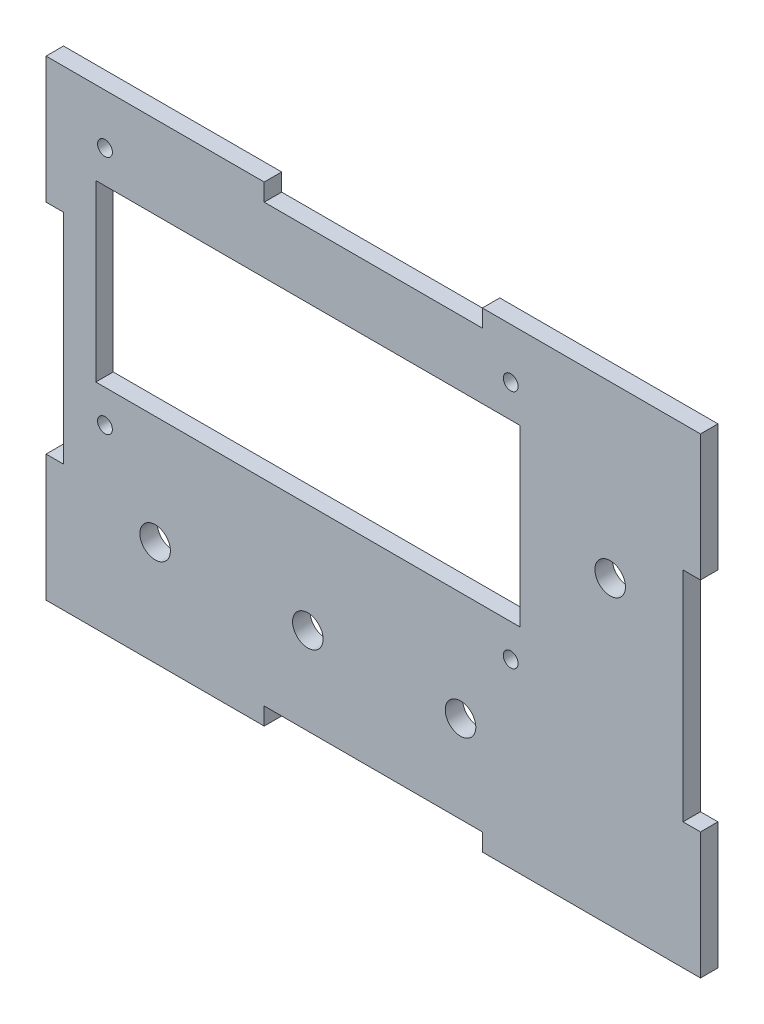
SolidWorks part; units mm, degrees
ref_plane "Front Plane" through (0, 0, 0) normal (0, 0, 1) x (1, 0, 0)
ref_plane "Top Plane" through (0, 0, 0) normal (0, 1, 0) x (1, 0, 0)
ref_plane "Right Plane" through (0, 0, 0) normal (1, 0, 0) x (0, 0, -1)
sketch "Sketch1" plane through (0, 0, 0) normal (0, 0, 1) x (1, 0, 0)
  line L1 (-75, -54) -> (75, -54)
  line L2 (-75, -54) -> (-75, 54)
  line L3 (-75, 54) -> (75, 54)
  line L4 (75, -54) -> (75, 54)
  line L5 (-75, -54) -> (75, 54) construction
  line L6 (-75, 54) -> (75, -54) construction
  point P0 (0, 0)
  dimension "D1" = 150
  dimension "D2" = 108
extrude "Plate" add sketch "Sketch1" along normal blind 4
sketch "Sketch2" plane through (0, 0, 0) normal (0, 0, -1) x (-1, 0, 0)
  line L1 (-33.6, -5) -> (63.6, -5)
  line L2 (-33.6, -5) -> (-33.6, 35)
  line L3 (-33.6, 35) -> (63.6, 35)
  line L4 (63.6, -5) -> (63.6, 35)
  line L5 (-33.6, -5) -> (63.6, 35) construction
  line L6 (-33.6, 35) -> (63.6, -5) construction
  point P0 (15, 15)
  dimension "D1" = 97.2
  dimension "D2" = 40
  dimension "D3" = 15
  dimension "D4" = 15
extrude "Screen slot" cut sketch "Sketch2" against normal through all
sketch "Screen screw hole position" plane through (0, 0, 0) normal (0, 0, -1) x (-1, 0, 0)
  line L0 (63.6, -5) -> (63.6, 35) construction
  line L1 (-33.6, -5) -> (63.6, -5) construction
  line L2 (-33.6, 35) -> (-33.6, -5) construction
  line L3 (63.6, 35) -> (-33.6, 35) construction
  line L4 (63.6, -5) -> (63.6, 35)
  line L5 (-33.6, -5) -> (63.6, -5)
  line L6 (-33.6, 35) -> (-33.6, -5)
  line L7 (63.6, 35) -> (-33.6, 35)
  line L8 (-33.6, 35) -> (63.6, -5) construction
  line L10 (-31.5, -12.5) -> (61.5, -12.5)
  line L11 (-31.5, -12.5) -> (-31.5, 42.5)
  line L12 (-31.5, 42.5) -> (61.5, 42.5)
  line L13 (61.5, -12.5) -> (61.5, 42.5)
  line L14 (-31.5, -12.5) -> (61.5, 42.5) construction
  line L15 (-31.5, 42.5) -> (61.5, -12.5) construction
  point P3 (15, 15)
  dimension "D1" = 93
  dimension "D2" = 55
hole_wizard "Screen screw holes" positions "3DSketch1" profile "Sketch5" countersink size "M3" standard "ISO" end condition up to next
sketch3d "3DSketch1"
  point P0 (31.5, 42.5, 0)
  point P3 (-61.5, 42.5, 0)
  point P6 (-61.5, -12.5, 0)
  point P9 (31.5, -12.5, 0)
sketch "Sketch5" plane through (31.5, 42.5, 0) normal (1, 0, 0) x (0, 1, 0)
  line L0 (0, 0) -> (0, 4)
  line L1 (0, 4) -> (1.7, 4)
  line L2 (1.7, 4) -> (1.7, 1.45)
  line L3 (1.7, 1.45) -> (3.15, 0)
  line L5 (3.15, 0) -> (0, 0)
  line L6 (-1.7, 1.45) -> (-3.15, 0) construction
  line L11 (0, -6.35) -> (0, 107.95) construction
  dimension "Thru Hole Dia." = 3.4
  dimension "Thru Hole Depth" = 4
  dimension "Near C'Sink Dia." = 6.3
  dimension "Near C'Sink Angle" = 90
sketch "Sketch6" plane through (0, 0, 0) normal (0, 0, -1) x (-1, 0, 0)
  line L0 (-75, -54) -> (-75, 54) construction
  line L1 (-33.6, 35) -> (-75, 35)
  line L2 (-33.6, 35) -> (-33.6, -5)
  line L3 (-33.6, -5) -> (-75, -5)
  line L4 (-75, 35) -> (-75, -5)
  line L5 (-75, 35) -> (-33.6, -5) construction
  line L6 (15, -5) -> (15, -30)
  line L7 (-33.6, -5) -> (63.6, -5) construction
  line L8 (15, -30) -> (50, -30)
  line L9 (15, -30) -> (-20, -30)
  point P7 (-54.3, 15)
  point P15 (37.915, -28.8748)
  dimension "D1" = 25
  dimension "D2" = 35
hole_wizard "Knob holes" positions "3DSketch2" profile "Sketch7" hole size "Ø6.0" standard "ISO" end condition up to next
sketch3d "3DSketch2"
  point P0 (20, -30, 0)
  point P3 (-15, -30, 0)
  point P6 (-50, -30, 0)
  point P9 (54.3, 15, 0)
sketch "Sketch7" plane through (20, -30, 0) normal (1, 0, 0) x (0, 1, 0)
  line L0 (0, 0) -> (0, 4)
  line L1 (0, 4) -> (3.5, 4)
  line L2 (3.5, 4) -> (3.5, 0)
  line L5 (3.5, 0) -> (0, 0)
  line L11 (0, -6.35) -> (0, 107.95) construction
  dimension "Thru Hole Dia." = 7
  dimension "Thru Hole Depth" = 4
sketch "Sketch8" plane through (0, 0, 0) normal (0, 0, -1) x (-1, 0, 0)
  line L0 (-75, 54) -> (75, 54) construction
  line L1 (-25, 54) -> (25, 54)
  line L2 (-25, 54) -> (-25, 50)
  line L3 (-25, 50) -> (25, 50)
  line L4 (25, 54) -> (25, 50)
  line L5 (-75, 54) -> (-25, 54)
  line L6 (25, 54) -> (75, 54)
  line L7 (-75, -54) -> (-75, 54) construction
  line L8 (-75, 25) -> (-71, 25)
  line L9 (-75, 25) -> (-75, -25)
  line L10 (-75, -25) -> (-71, -25)
  line L11 (-71, 25) -> (-71, -25)
  line L12 (-75, 25) -> (-75, 54)
  line L13 (-75, -25) -> (-75, -54)
  line L14 (0, 2.2) -> (0, -2.2) construction
  line L15 (75, -25) -> (71, -25)
  line L16 (71, 25) -> (71, -25)
  line L17 (75, 25) -> (71, 25)
  line L18 (75, 25) -> (75, -25)
  line L19 (2.2, 0) -> (-2.2, 0) construction
  line L20 (-25, -50) -> (25, -50)
  line L21 (25, -54) -> (25, -50)
  line L22 (-25, -54) -> (25, -54)
  line L23 (-25, -54) -> (-25, -50)
  line M25 (-75, 54) -> (-75, -54)
  line M26 (-75, -54) -> (75, -54)
  line M27 (75, -54) -> (75, 54)
  line M28 (75, 54) -> (-75, 54)
  dimension "D1" = 50
  dimension "D2" = 4
  dimension "D3" = 50
  dimension "D4" = 4
extrude "Cut-Extrude2" cut sketch "Sketch8" against normal up to next contours L4 L2 L3 M28 | L17 L16 L15 M27 | L23 L21 L20 M26 | L11 L8 L10 M25 region at (0, 52, 0) region at (73, 0, 0) region at (-73, 0, 0) region at (0, -52, 0)
